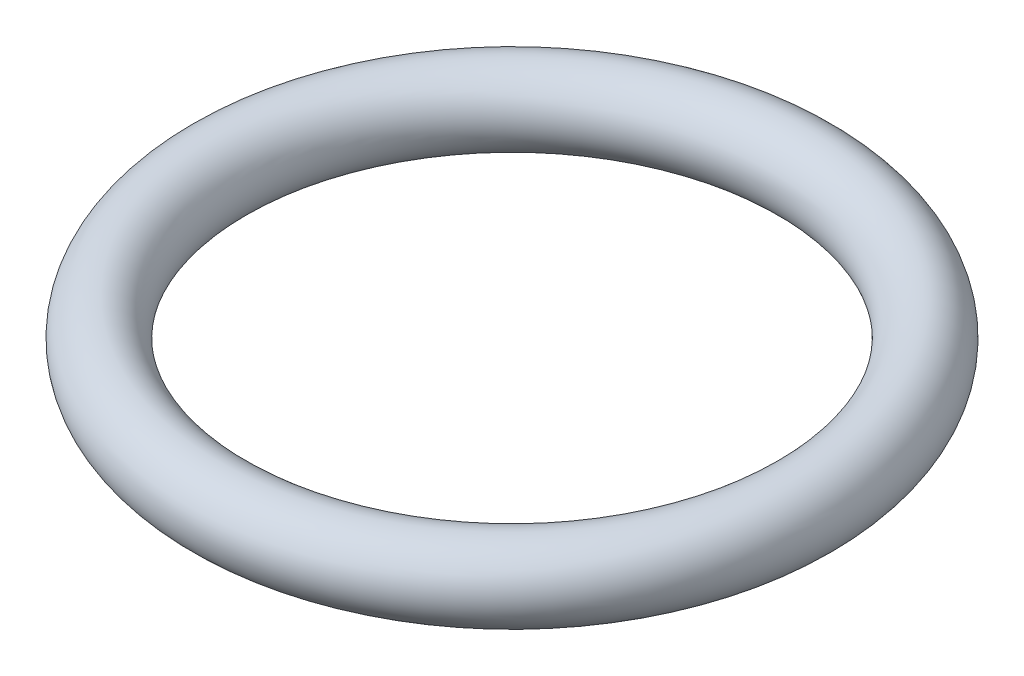
SolidWorks part; units mm, degrees
ref_plane "Front Plane" through (0, 0, 0) normal (0, 0, 1) x (1, 0, 0)
ref_plane "Top Plane" through (0, 0, 0) normal (0, 1, 0) x (1, 0, 0)
ref_plane "Right Plane" through (0, 0, 0) normal (1, 0, 0) x (0, 0, -1)
sketch "Sketch1" plane through (0, 0, 0) normal (0, 1, 0) x (1, 0, 0)
  line L0 (0, 0) -> (20, 0)
  circle A0 centre (0, 0) radius 5
  circle A1 centre (20, 0) radius 2.5
  dimension "D1" = 10
  dimension "D3" = 5
  dimension "D2" = 20
sketch "Sketch3" plane through (0, 0, 0) normal (0, 0, 1) x (1, 0, 0)
  line L0 (-4.9876, 0) -> (4.9876, 0)
  line L2 (-4.9876, 0) -> (-4.9876, -8.4044)
  line L3 (-4.9876, -8.4044) -> (4.9876, -8.4044)
  line L4 (4.9876, 0) -> (4.9876, -8.4044)
  line L5 (0, 0) -> (4.9876, -8.4044) construction
  line L6 (-4.9876, -8.4044) -> (0, 0) construction
  arc A0 (4.9876, -8.4044) -> (0, -20.158) centre (-3.383, -11.7875) cw
  arc A1 (-4.9876, -8.4044) -> (-6.1585, -10.75) centre (-6.7458, -8.9917) cw
  arc A2 (-6.1585, -10.75) -> (-16.6986, -15.4351) centre (-9.1232, -18.2789) ccw
  arc A3 (0, -20.158) -> (19.4121, -31.3753) centre (10.1638, -24.9745) ccw
  arc A4 (-16.6986, -15.4351) -> (36.4784, -31.3751) centre (9.348, -25.2129) ccw
  arc A5 (19.4121, -31.3753) -> (38.1158, -23.9493) centre (32.477, -37.0141) cw
  arc A6 (36.4784, -31.3751) -> (38.1158, -23.9493) centre (41.01, -28.4809) cw
  circle A7 centre (41.01, -28.4809) radius 5.2459
  point P0 (0, 0)
sweep "Sweep1" add profiles "Sketch3" path "Sketch1"
